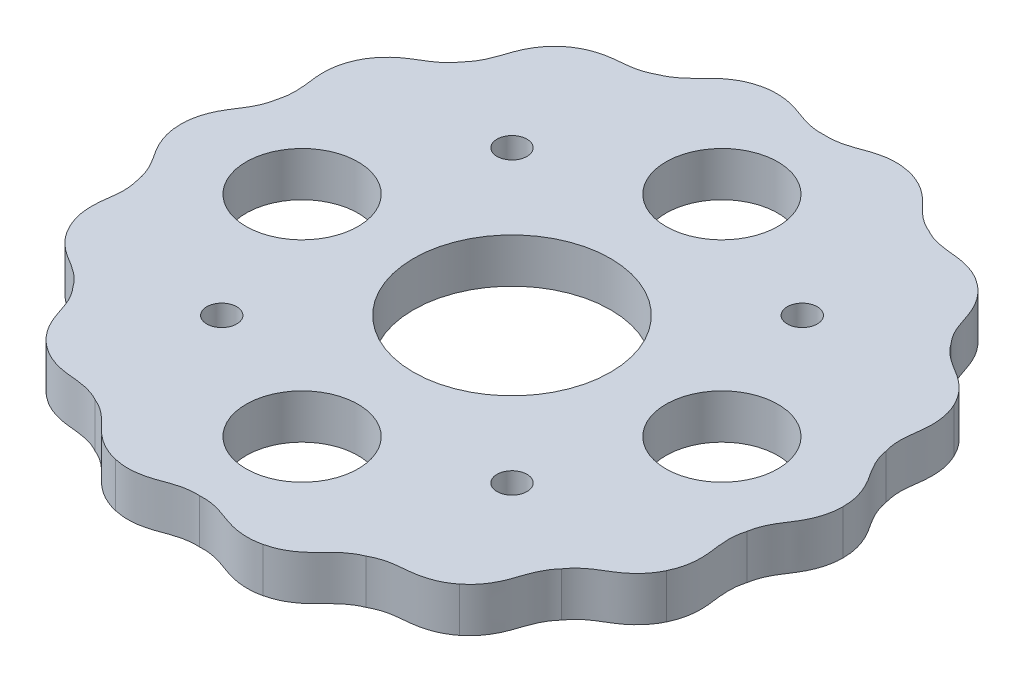
SolidWorks part; units mm, degrees
ref_plane "Front Plane" through (0, 0, 0) normal (0, 0, 1) x (1, 0, 0)
ref_plane "Top Plane" through (0, 0, 0) normal (0, 1, 0) x (1, 0, 0)
ref_plane "Right Plane" through (0, 0, 0) normal (1, 0, 0) x (0, 0, -1)
sketch "Sketch1" plane through (0, 0, 0) normal (0, 1, 0) x (1, 0, 0)
  line L0 (0, 0) -> (37.5, 0) construction
  line L1 (0, 0) -> (37.4807, 1.2019) construction
  line L2 (0, 0) -> (37.423, 2.4026) construction
  line L3 (0, 0) -> (37.3267, 3.6009) construction
  line L4 (0, 0) -> (37.1921, 4.7954) construction
  line L5 (0, 0) -> (37.0193, 5.985) construction
  line L6 (0, 0) -> (36.8085, 7.1684) construction
  line L7 (0, 0) -> (36.5598, 8.3445) construction
  line L8 (0, 0) -> (36.2736, 9.512) construction
  line L9 (0, 0) -> (35.95, 10.6698) construction
  line L10 (0, 0) -> (35.5896, 11.8166) construction
  line L11 (0, 0) -> (35.1926, 12.9512) construction
  line L12 (0, 0) -> (34.7594, 14.0725) construction
  line L13 (0, 0) -> (34.2905, 15.1794) construction
  line L14 (0, 0) -> (33.7863, 16.2706) construction
  line L15 (37.5, 0) -> (38.5, 0) construction
  line L16 (37.4807, 1.2019) -> (38.3521, 1.6927) construction
  line L17 (37.423, 2.4026) -> (37.9413, 3.2578) construction
  line L18 (37.3267, 3.6009) -> (37.3588, 4.6003) construction
  line L19 (37.1921, 4.7954) -> (36.7296, 5.682) construction
  line L20 (37.0193, 5.985) -> (36.1812, 6.5305) construction
  line L21 (36.8085, 7.1684) -> (35.8105, 7.2325) construction
  line L22 (36.5598, 8.3445) -> (35.5849, 8.122) construction
  line L23 (37, 0.0019) -> (37, 0)
  line L24 (33.3367, 16.052) -> (33.3358, 16.0537)
  line L25 (37, -0.0019) -> (37, 0)
  line L26 (33.3367, -16.052) -> (33.3358, -16.0537)
  line L27 (33.335, -16.0554) -> (33.3358, -16.0537)
  line L28 (23.0706, -28.9266) -> (23.0691, -28.9278)
  line L29 (23.0677, -28.9289) -> (23.0691, -28.9278)
  line L30 (8.2351, -36.0719) -> (8.2333, -36.0723)
  line L31 (8.2315, -36.0727) -> (8.2333, -36.0723)
  line L32 (-8.2315, -36.0727) -> (-8.2333, -36.0723)
  line L33 (-8.2351, -36.0719) -> (-8.2333, -36.0723)
  line L34 (-23.0677, -28.9289) -> (-23.0691, -28.9278)
  line L35 (-23.0706, -28.9266) -> (-23.0691, -28.9278)
  line L36 (-33.335, -16.0554) -> (-33.3358, -16.0537)
  line L37 (-33.3367, -16.052) -> (-33.3358, -16.0537)
  line L38 (-37, -0.0019) -> (-37, 0)
  line L39 (-37, 0.0019) -> (-37, 0)
  line L40 (-33.3367, 16.052) -> (-33.3358, 16.0537)
  line L41 (-33.335, 16.0554) -> (-33.3358, 16.0537)
  line L42 (-23.0706, 28.9266) -> (-23.0691, 28.9278)
  line L43 (-23.0677, 28.9289) -> (-23.0691, 28.9278)
  line L44 (-8.2351, 36.0719) -> (-8.2333, 36.0723)
  line L45 (-8.2315, 36.0727) -> (-8.2333, 36.0723)
  line L46 (8.2315, 36.0727) -> (8.2333, 36.0723)
  line L47 (8.2351, 36.0719) -> (8.2333, 36.0723)
  line L48 (23.0677, 28.9289) -> (23.0691, 28.9278)
  line L49 (23.0706, 28.9266) -> (23.0691, 28.9278)
  line L50 (33.335, 16.0554) -> (33.3358, 16.0537)
  line L51 (35.5, 0.0037) -> (35.5, 0)
  line L52 (31.986, 15.3995) -> (31.9844, 15.4029)
  line L53 (35.5, -0.0037) -> (35.5, 0)
  line L54 (31.986, -15.3995) -> (31.9844, -15.4029)
  line L55 (31.9828, -15.4062) -> (31.9844, -15.4029)
  line L56 (22.1368, -27.7527) -> (22.1339, -27.755)
  line L57 (22.131, -27.7573) -> (22.1339, -27.755)
  line L58 (7.9031, -34.6091) -> (7.8995, -34.6099)
  line L59 (7.8959, -34.6108) -> (7.8995, -34.6099)
  line L60 (-7.8959, -34.6108) -> (-7.8995, -34.6099)
  line L61 (-7.9031, -34.6091) -> (-7.8995, -34.6099)
  line L62 (-22.131, -27.7573) -> (-22.1339, -27.755)
  line L63 (-22.1368, -27.7527) -> (-22.1339, -27.755)
  line L64 (-31.9828, -15.4062) -> (-31.9844, -15.4029)
  line L65 (-31.986, -15.3995) -> (-31.9844, -15.4029)
  line L66 (-35.5, -0.0037) -> (-35.5, 0)
  line L67 (-35.5, 0.0037) -> (-35.5, 0)
  line L68 (-31.986, 15.3995) -> (-31.9844, 15.4029)
  line L69 (-31.9828, 15.4062) -> (-31.9844, 15.4029)
  line L70 (-22.1368, 27.7527) -> (-22.1339, 27.755)
  line L71 (-22.131, 27.7573) -> (-22.1339, 27.755)
  line L72 (-7.9031, 34.6091) -> (-7.8995, 34.6099)
  line L73 (-7.8959, 34.6108) -> (-7.8995, 34.6099)
  line L74 (7.8959, 34.6108) -> (7.8995, 34.6099)
  line L75 (7.9031, 34.6091) -> (7.8995, 34.6099)
  line L76 (22.131, 27.7573) -> (22.1339, 27.755)
  line L77 (22.1368, 27.7527) -> (22.1339, 27.755)
  line L78 (31.9828, 15.4062) -> (31.9844, 15.4029)
  circle A0 centre (0, 0) radius 35 construction
  circle A1 centre (37.5, 0) radius 2.5 construction
  circle A2 centre (0, 0) radius 37.5 construction
  spline S0 degree 3 poles (35.5849, 8.122) (35.6266, 7.5364) (36.0345, 6.7125) (36.7836, 5.6218) (37.4152, 4.5501) (38.2239, 2.702) (38.5014, 1.1074) (38.5, 0) knots 0 0 0 0 0.195516 0.310928 0.453873 0.621058 1 1 1 1
  spline S1 degree 3 poles (35.5849, 8.122) (35.3683, 8.6678) (35.3784, 9.5871) (35.5801, 10.8948) (35.6841, 12.1344) (35.611, 14.1503) (35.169, 15.7074) (34.6873, 16.7045) knots 0 0 0 0 0.195516 0.310928 0.453873 0.621058 1 1 1 1
  spline S2 degree 1 poles (34.1119, 7.7858) (33.3367, 16.052) knots 0 0 1 1 construction
  spline S3 degree 1 poles (34.1119, 7.7858) (37, 0.0019) knots 0 0 1 1 construction
  spline S4 degree 3 poles (33.3367, 16.052) (33.6005, 15.5058) (33.9037, 14.6401) (34.1146, 13.4372) (34.174, 12.5211) (34.1413, 11.5771) (34.0239, 10.6392) (33.8823, 9.6155) (33.9055, 8.625) (34.0243, 8.0514) (34.1119, 7.7858) knots 0.015853 0.015853 0.015853 0.015853 0.26189 0.384908 0.507927 0.630945 0.753963 0.876982 0.938491 1 1 1 1
  spline S5 degree 3 poles (34.1119, 7.7858) (34.1483, 7.5085) (34.2901, 6.9402) (34.6989, 6.0377) (35.2706, 5.1769) (35.7834, 4.3828) (36.2224, 3.5464) (36.5664, 2.6953) (36.8983, 1.52) (37.0008, 0.6085) (37, 0.0019) knots 0.015853 0.015853 0.015853 0.015853 0.077362 0.138872 0.26189 0.384908 0.507927 0.630945 0.753963 1 1 1 1
  spline S6 degree 3 poles (37, -0.0019) (37.0008, -0.6085) (36.8983, -1.52) (36.5664, -2.6953) (36.2224, -3.5464) (35.7834, -4.3828) (35.2706, -5.1769) (34.6989, -6.0377) (34.2901, -6.9402) (34.1483, -7.5085) (34.1119, -7.7858) knots 0.015853 0.015853 0.015853 0.015853 0.26189 0.384908 0.507927 0.630945 0.753963 0.876982 0.938491 1 1 1 1
  spline S7 degree 3 poles (34.1119, -7.7858) (34.0243, -8.0514) (33.9055, -8.625) (33.8823, -9.6155) (34.0239, -10.6392) (34.1413, -11.5771) (34.174, -12.5211) (34.1146, -13.4372) (33.9037, -14.6401) (33.6005, -15.5058) (33.3367, -16.052) knots 0.015853 0.015853 0.015853 0.015853 0.077362 0.138872 0.26189 0.384908 0.507927 0.630945 0.753963 1 1 1 1
  spline S8 degree 3 poles (33.335, -16.0554) (33.0725, -16.6022) (32.5847, -17.3791) (31.7758, -18.2939) (31.0965, -18.9115) (30.3381, -19.4746) (29.5316, -19.9675) (28.6429, -20.4951) (27.8831, -21.1308) (27.5087, -21.5813) (27.3556, -21.8154) knots 0.015853 0.015853 0.015853 0.015853 0.26189 0.384908 0.507927 0.630945 0.753963 0.876982 0.938491 1 1 1 1
  spline S9 degree 3 poles (27.3556, -21.8154) (27.1615, -22.0167) (26.8056, -22.4819) (26.3549, -23.3642) (26.0383, -24.348) (25.7371, -25.2439) (25.357, -26.1087) (24.906, -26.9083) (24.1941, -27.9005) (23.5453, -28.549) (23.0706, -28.9266) knots 0.015853 0.015853 0.015853 0.015853 0.077362 0.138872 0.26189 0.384908 0.507927 0.630945 0.753963 1 1 1 1
  spline S10 degree 3 poles (23.0677, -28.9289) (22.5939, -29.3077) (21.8173, -29.796) (20.6915, -30.2693) (19.8116, -30.531) (18.884, -30.7092) (17.9435, -30.8034) (16.9139, -30.8931) (15.9535, -31.1362) (15.4207, -31.3797) (15.1812, -31.5241) knots 0.015853 0.015853 0.015853 0.015853 0.26189 0.384908 0.507927 0.630945 0.753963 0.876982 0.938491 1 1 1 1
  spline S11 degree 3 poles (15.1812, -31.5241) (14.919, -31.6213) (14.3964, -31.886) (13.6076, -32.4854) (12.8955, -33.2344) (12.2354, -33.9109) (11.5177, -34.5251) (10.7645, -35.0499) (9.6926, -35.6349) (8.8266, -35.9377) (8.2351, -36.0719) knots 0.015853 0.015853 0.015853 0.015853 0.077362 0.138872 0.26189 0.384908 0.507927 0.630945 0.753963 1 1 1 1
  spline S12 degree 3 poles (8.2315, -36.0727) (7.6402, -36.2085) (6.7287, -36.3114) (5.5091, -36.2494) (4.6028, -36.1034) (3.6897, -35.8614) (2.8014, -35.5383) (1.8349, -35.1724) (0.8641, -34.9747) (0.2785, -34.9629) (0, -34.9891) knots 0.015853 0.015853 0.015853 0.015853 0.26189 0.384908 0.507927 0.630945 0.753963 0.876982 0.938491 1 1 1 1
  spline S13 degree 3 poles (0, -34.9891) (-0.2785, -34.9629) (-0.8641, -34.9747) (-1.8349, -35.1724) (-2.8014, -35.5383) (-3.6897, -35.8614) (-4.6028, -36.1034) (-5.5091, -36.2494) (-6.7287, -36.3114) (-7.6402, -36.2085) (-8.2315, -36.0727) knots 0.015853 0.015853 0.015853 0.015853 0.077362 0.138872 0.26189 0.384908 0.507927 0.630945 0.753963 1 1 1 1
  spline S14 degree 3 poles (-8.2351, -36.0719) (-8.8266, -35.9377) (-9.6926, -35.6349) (-10.7645, -35.0499) (-11.5177, -34.5251) (-12.2354, -33.9109) (-12.8955, -33.2344) (-13.6076, -32.4854) (-14.3964, -31.886) (-14.919, -31.6213) (-15.1812, -31.5241) knots 0.015853 0.015853 0.015853 0.015853 0.26189 0.384908 0.507927 0.630945 0.753963 0.876982 0.938491 1 1 1 1
  spline S15 degree 3 poles (-15.1812, -31.5241) (-15.4207, -31.3797) (-15.9535, -31.1362) (-16.9139, -30.8931) (-17.9435, -30.8034) (-18.884, -30.7092) (-19.8116, -30.531) (-20.6915, -30.2693) (-21.8173, -29.796) (-22.5939, -29.3077) (-23.0677, -28.9289) knots 0.015853 0.015853 0.015853 0.015853 0.077362 0.138872 0.26189 0.384908 0.507927 0.630945 0.753963 1 1 1 1
  spline S16 degree 3 poles (-23.0706, -28.9266) (-23.5453, -28.549) (-24.1941, -27.9005) (-24.906, -26.9083) (-25.357, -26.1087) (-25.7371, -25.2439) (-26.0383, -24.348) (-26.3549, -23.3642) (-26.8056, -22.4819) (-27.1615, -22.0167) (-27.3556, -21.8154) knots 0.015853 0.015853 0.015853 0.015853 0.26189 0.384908 0.507927 0.630945 0.753963 0.876982 0.938491 1 1 1 1
  spline S17 degree 3 poles (-27.3556, -21.8154) (-27.5087, -21.5813) (-27.8831, -21.1308) (-28.6429, -20.4951) (-29.5316, -19.9675) (-30.3381, -19.4746) (-31.0965, -18.9115) (-31.7758, -18.2939) (-32.5847, -17.3791) (-33.0725, -16.6022) (-33.335, -16.0554) knots 0.015853 0.015853 0.015853 0.015853 0.077362 0.138872 0.26189 0.384908 0.507927 0.630945 0.753963 1 1 1 1
  spline S18 degree 3 poles (-33.3367, -16.052) (-33.6005, -15.5058) (-33.9037, -14.6401) (-34.1146, -13.4372) (-34.174, -12.5211) (-34.1413, -11.5771) (-34.0239, -10.6392) (-33.8823, -9.6155) (-33.9055, -8.625) (-34.0243, -8.0514) (-34.1119, -7.7858) knots 0.015853 0.015853 0.015853 0.015853 0.26189 0.384908 0.507927 0.630945 0.753963 0.876982 0.938491 1 1 1 1
  spline S19 degree 3 poles (-34.1119, -7.7858) (-34.1483, -7.5085) (-34.2901, -6.9402) (-34.6989, -6.0377) (-35.2706, -5.1769) (-35.7834, -4.3828) (-36.2224, -3.5464) (-36.5664, -2.6953) (-36.8983, -1.52) (-37.0008, -0.6085) (-37, -0.0019) knots 0.015853 0.015853 0.015853 0.015853 0.077362 0.138872 0.26189 0.384908 0.507927 0.630945 0.753963 1 1 1 1
  spline S20 degree 3 poles (-37, 0.0019) (-37.0008, 0.6085) (-36.8983, 1.52) (-36.5664, 2.6953) (-36.2224, 3.5464) (-35.7834, 4.3828) (-35.2706, 5.1769) (-34.6989, 6.0377) (-34.2901, 6.9402) (-34.1483, 7.5085) (-34.1119, 7.7858) knots 0.015853 0.015853 0.015853 0.015853 0.26189 0.384908 0.507927 0.630945 0.753963 0.876982 0.938491 1 1 1 1
  spline S21 degree 3 poles (-34.1119, 7.7858) (-34.0243, 8.0514) (-33.9055, 8.625) (-33.8823, 9.6155) (-34.0239, 10.6392) (-34.1413, 11.5771) (-34.174, 12.5211) (-34.1146, 13.4372) (-33.9037, 14.6401) (-33.6005, 15.5058) (-33.3367, 16.052) knots 0.015853 0.015853 0.015853 0.015853 0.077362 0.138872 0.26189 0.384908 0.507927 0.630945 0.753963 1 1 1 1
  spline S22 degree 3 poles (-33.335, 16.0554) (-33.0725, 16.6022) (-32.5847, 17.3791) (-31.7758, 18.2939) (-31.0965, 18.9115) (-30.3381, 19.4746) (-29.5316, 19.9675) (-28.6429, 20.4951) (-27.8831, 21.1308) (-27.5087, 21.5813) (-27.3556, 21.8154) knots 0.015853 0.015853 0.015853 0.015853 0.26189 0.384908 0.507927 0.630945 0.753963 0.876982 0.938491 1 1 1 1
  spline S23 degree 3 poles (-27.3556, 21.8154) (-27.1615, 22.0167) (-26.8056, 22.4819) (-26.3549, 23.3642) (-26.0383, 24.348) (-25.7371, 25.2439) (-25.357, 26.1087) (-24.906, 26.9083) (-24.1941, 27.9005) (-23.5453, 28.549) (-23.0706, 28.9266) knots 0.015853 0.015853 0.015853 0.015853 0.077362 0.138872 0.26189 0.384908 0.507927 0.630945 0.753963 1 1 1 1
  spline S24 degree 3 poles (-23.0677, 28.9289) (-22.5939, 29.3077) (-21.8173, 29.796) (-20.6915, 30.2693) (-19.8116, 30.531) (-18.884, 30.7092) (-17.9435, 30.8034) (-16.9139, 30.8931) (-15.9535, 31.1362) (-15.4207, 31.3797) (-15.1812, 31.5241) knots 0.015853 0.015853 0.015853 0.015853 0.26189 0.384908 0.507927 0.630945 0.753963 0.876982 0.938491 1 1 1 1
  spline S25 degree 3 poles (-15.1812, 31.5241) (-14.919, 31.6213) (-14.3964, 31.886) (-13.6076, 32.4854) (-12.8955, 33.2344) (-12.2354, 33.9109) (-11.5177, 34.5251) (-10.7645, 35.0499) (-9.6926, 35.6349) (-8.8266, 35.9377) (-8.2351, 36.0719) knots 0.015853 0.015853 0.015853 0.015853 0.077362 0.138872 0.26189 0.384908 0.507927 0.630945 0.753963 1 1 1 1
  spline S26 degree 3 poles (-8.2315, 36.0727) (-7.6402, 36.2085) (-6.7287, 36.3114) (-5.5091, 36.2494) (-4.6028, 36.1034) (-3.6897, 35.8614) (-2.8014, 35.5383) (-1.8349, 35.1724) (-0.8641, 34.9747) (-0.2785, 34.9629) (0, 34.9891) knots 0.015853 0.015853 0.015853 0.015853 0.26189 0.384908 0.507927 0.630945 0.753963 0.876982 0.938491 1 1 1 1
  spline S27 degree 3 poles (0, 34.9891) (0.2785, 34.9629) (0.8641, 34.9747) (1.8349, 35.1724) (2.8014, 35.5383) (3.6897, 35.8614) (4.6028, 36.1034) (5.5091, 36.2494) (6.7287, 36.3114) (7.6402, 36.2085) (8.2315, 36.0727) knots 0.015853 0.015853 0.015853 0.015853 0.077362 0.138872 0.26189 0.384908 0.507927 0.630945 0.753963 1 1 1 1
  spline S28 degree 3 poles (8.2351, 36.0719) (8.8266, 35.9377) (9.6926, 35.6349) (10.7645, 35.0499) (11.5177, 34.5251) (12.2354, 33.9109) (12.8955, 33.2344) (13.6076, 32.4854) (14.3964, 31.886) (14.919, 31.6213) (15.1812, 31.5241) knots 0.015853 0.015853 0.015853 0.015853 0.26189 0.384908 0.507927 0.630945 0.753963 0.876982 0.938491 1 1 1 1
  spline S29 degree 3 poles (15.1812, 31.5241) (15.4207, 31.3797) (15.9535, 31.1362) (16.9139, 30.8931) (17.9435, 30.8034) (18.884, 30.7092) (19.8116, 30.531) (20.6915, 30.2693) (21.8173, 29.796) (22.5939, 29.3077) (23.0677, 28.9289) knots 0.015853 0.015853 0.015853 0.015853 0.077362 0.138872 0.26189 0.384908 0.507927 0.630945 0.753963 1 1 1 1
  spline S30 degree 3 poles (23.0706, 28.9266) (23.5453, 28.549) (24.1941, 27.9005) (24.906, 26.9083) (25.357, 26.1087) (25.7371, 25.2439) (26.0383, 24.348) (26.3549, 23.3642) (26.8056, 22.4819) (27.1615, 22.0167) (27.3556, 21.8154) knots 0.015853 0.015853 0.015853 0.015853 0.26189 0.384908 0.507927 0.630945 0.753963 0.876982 0.938491 1 1 1 1
  spline S31 degree 3 poles (27.3556, 21.8154) (27.5087, 21.5813) (27.8831, 21.1308) (28.6429, 20.4951) (29.5316, 19.9675) (30.3381, 19.4746) (31.0965, 18.9115) (31.7758, 18.2939) (32.5847, 17.3791) (33.0725, 16.6022) (33.335, 16.0554) knots 0.015853 0.015853 0.015853 0.015853 0.077362 0.138872 0.26189 0.384908 0.507927 0.630945 0.753963 1 1 1 1
  spline S32 degree 1 poles (32.6448, 7.451) (35.5, 0.0037) knots 0 0 1 1 construction
  spline S33 degree 1 poles (32.6448, 7.451) (31.986, 15.3995) knots 0 0 1 1 construction
  spline S34 degree 3 poles (35.5, 0.0037) (35.5006, 0.4959) (35.4183, 1.2336) (35.1496, 2.1927) (34.8707, 2.8896) (34.4997, 3.6015) (34.1394, 4.1652) (33.6939, 4.8394) (33.3068, 5.4873) (32.9751, 6.1975) (32.758, 6.8733) (32.6748, 7.2607) (32.6448, 7.451) knots 0.023011 0.023011 0.023011 0.023011 0.267258 0.389382 0.511505 0.633629 0.755753 0.816814 0.877876 0.938938 0.969469 1 1 1 1
  spline S35 degree 3 poles (32.6448, 7.451) (32.5893, 7.6354) (32.4961, 8.0206) (32.3985, 8.7236) (32.3893, 9.5074) (32.4569, 10.2591) (32.5657, 11.0598) (32.6458, 11.724) (32.6712, 12.5264) (32.6201, 13.2752) (32.446, 14.256) (32.2001, 14.9563) (31.986, 15.3995) knots 0.023011 0.023011 0.023011 0.023011 0.053542 0.084072 0.145134 0.206196 0.267258 0.389382 0.511505 0.633629 0.755753 1 1 1 1
  spline S36 degree 3 poles (32.6448, -7.451) (32.6748, -7.2607) (32.758, -6.8733) (32.9751, -6.1975) (33.3068, -5.4873) (33.6939, -4.8394) (34.1394, -4.1652) (34.4997, -3.6015) (34.8707, -2.8896) (35.1496, -2.1927) (35.4183, -1.2336) (35.5006, -0.4959) (35.5, -0.0037) knots 0.023011 0.023011 0.023011 0.023011 0.053542 0.084072 0.145134 0.206196 0.267258 0.389382 0.511505 0.633629 0.755753 1 1 1 1
  spline S37 degree 3 poles (31.986, -15.3995) (32.2001, -14.9563) (32.446, -14.256) (32.6201, -13.2752) (32.6712, -12.5264) (32.6458, -11.724) (32.5657, -11.0598) (32.4569, -10.2591) (32.3893, -9.5074) (32.3985, -8.7236) (32.4961, -8.0206) (32.5893, -7.6354) (32.6448, -7.451) knots 0.023011 0.023011 0.023011 0.023011 0.267258 0.389382 0.511505 0.633629 0.755753 0.816814 0.877876 0.938938 0.969469 1 1 1 1
  spline S38 degree 3 poles (26.1791, -20.8771) (26.2887, -20.7187) (26.5317, -20.4057) (27.0205, -19.8911) (27.6275, -19.3952) (28.2574, -18.9793) (28.9513, -18.5652) (29.5206, -18.2137) (30.1637, -17.7333) (30.7173, -17.2264) (31.3755, -16.4789) (31.7698, -15.8499) (31.9828, -15.4062) knots 0.023011 0.023011 0.023011 0.023011 0.053542 0.084072 0.145134 0.206196 0.267258 0.389382 0.511505 0.633629 0.755753 1 1 1 1
  spline S39 degree 3 poles (22.1368, -27.7527) (22.522, -27.4463) (23.0474, -26.922) (23.6297, -26.1139) (24.0007, -25.4614) (24.326, -24.7275) (24.542, -24.0943) (24.7914, -23.3257) (25.0566, -22.619) (25.405, -21.9169) (25.798, -21.3258) (26.0491, -21.0192) (26.1791, -20.8771) knots 0.023011 0.023011 0.023011 0.023011 0.267258 0.389382 0.511505 0.633629 0.755753 0.816814 0.877876 0.938938 0.969469 1 1 1 1
  spline S40 degree 3 poles (14.5283, -30.1683) (14.6957, -30.0732) (15.0505, -29.8966) (15.7143, -29.645) (16.4763, -29.4616) (17.2242, -29.3602) (18.0291, -29.2882) (18.6945, -29.2185) (19.4823, -29.0647) (20.201, -28.8482) (21.1184, -28.4603) (21.7465, -28.0647) (22.131, -27.7573) knots 0.023011 0.023011 0.023011 0.023011 0.053542 0.084072 0.145134 0.206196 0.267258 0.389382 0.511505 0.633629 0.755753 1 1 1 1
  spline S41 degree 3 poles (7.9031, -34.6091) (8.3831, -34.5002) (9.084, -34.2557) (9.9593, -33.7804) (10.5766, -33.3534) (11.1881, -32.8334) (11.6575, -32.3566) (12.2156, -31.7723) (12.7612, -31.2507) (13.3797, -30.7693) (13.9903, -30.4072) (14.3495, -30.2399) (14.5283, -30.1683) knots 0.023011 0.023011 0.023011 0.023011 0.267258 0.389382 0.511505 0.633629 0.755753 0.816814 0.877876 0.938938 0.969469 1 1 1 1
  spline S42 degree 3 poles (0, -33.4843) (0.1922, -33.4712) (0.5884, -33.4661) (1.2956, -33.5274) (2.0617, -33.6928) (2.7796, -33.926) (3.536, -34.2103) (4.1657, -34.4362) (4.9423, -34.6394) (5.6838, -34.7562) (6.6786, -34.8048) (7.4161, -34.7209) (7.8959, -34.6108) knots 0.023011 0.023011 0.023011 0.023011 0.053542 0.084072 0.145134 0.206196 0.267258 0.389382 0.511505 0.633629 0.755753 1 1 1 1
  spline S43 degree 3 poles (-7.8959, -34.6108) (-7.4161, -34.7209) (-6.6786, -34.8048) (-5.6838, -34.7562) (-4.9423, -34.6394) (-4.1657, -34.4362) (-3.536, -34.2103) (-2.7796, -33.926) (-2.0617, -33.6928) (-1.2956, -33.5274) (-0.5884, -33.4661) (-0.1922, -33.4712) (0, -33.4843) knots 0.023011 0.023011 0.023011 0.023011 0.267258 0.389382 0.511505 0.633629 0.755753 0.816814 0.877876 0.938938 0.969469 1 1 1 1
  spline S44 degree 3 poles (-14.5283, -30.1683) (-14.3495, -30.2399) (-13.9903, -30.4072) (-13.3797, -30.7693) (-12.7612, -31.2507) (-12.2156, -31.7723) (-11.6575, -32.3566) (-11.1881, -32.8334) (-10.5766, -33.3534) (-9.9593, -33.7804) (-9.084, -34.2557) (-8.3831, -34.5002) (-7.9031, -34.6091) knots 0.023011 0.023011 0.023011 0.023011 0.053542 0.084072 0.145134 0.206196 0.267258 0.389382 0.511505 0.633629 0.755753 1 1 1 1
  spline S45 degree 3 poles (-22.131, -27.7573) (-21.7465, -28.0647) (-21.1184, -28.4603) (-20.201, -28.8482) (-19.4823, -29.0647) (-18.6945, -29.2185) (-18.0291, -29.2882) (-17.2242, -29.3602) (-16.4763, -29.4616) (-15.7143, -29.645) (-15.0505, -29.8966) (-14.6957, -30.0732) (-14.5283, -30.1683) knots 0.023011 0.023011 0.023011 0.023011 0.267258 0.389382 0.511505 0.633629 0.755753 0.816814 0.877876 0.938938 0.969469 1 1 1 1
  spline S46 degree 3 poles (-26.1791, -20.8771) (-26.0491, -21.0192) (-25.798, -21.3258) (-25.405, -21.9169) (-25.0566, -22.619) (-24.7914, -23.3257) (-24.542, -24.0943) (-24.326, -24.7275) (-24.0007, -25.4614) (-23.6297, -26.1139) (-23.0474, -26.922) (-22.522, -27.4463) (-22.1368, -27.7527) knots 0.023011 0.023011 0.023011 0.023011 0.053542 0.084072 0.145134 0.206196 0.267258 0.389382 0.511505 0.633629 0.755753 1 1 1 1
  spline S47 degree 3 poles (-31.9828, -15.4062) (-31.7698, -15.8499) (-31.3755, -16.4789) (-30.7173, -17.2264) (-30.1637, -17.7333) (-29.5206, -18.2137) (-28.9513, -18.5652) (-28.2574, -18.9793) (-27.6275, -19.3952) (-27.0205, -19.8911) (-26.5317, -20.4057) (-26.2887, -20.7187) (-26.1791, -20.8771) knots 0.023011 0.023011 0.023011 0.023011 0.267258 0.389382 0.511505 0.633629 0.755753 0.816814 0.877876 0.938938 0.969469 1 1 1 1
  spline S48 degree 3 poles (-32.6448, -7.451) (-32.5893, -7.6354) (-32.4961, -8.0206) (-32.3985, -8.7236) (-32.3893, -9.5074) (-32.4569, -10.2591) (-32.5657, -11.0598) (-32.6458, -11.724) (-32.6712, -12.5264) (-32.6201, -13.2752) (-32.446, -14.256) (-32.2001, -14.9563) (-31.986, -15.3995) knots 0.023011 0.023011 0.023011 0.023011 0.053542 0.084072 0.145134 0.206196 0.267258 0.389382 0.511505 0.633629 0.755753 1 1 1 1
  spline S49 degree 3 poles (-35.5, -0.0037) (-35.5006, -0.4959) (-35.4183, -1.2336) (-35.1496, -2.1927) (-34.8707, -2.8896) (-34.4997, -3.6015) (-34.1394, -4.1652) (-33.6939, -4.8394) (-33.3068, -5.4873) (-32.9751, -6.1975) (-32.758, -6.8733) (-32.6748, -7.2607) (-32.6448, -7.451) knots 0.023011 0.023011 0.023011 0.023011 0.267258 0.389382 0.511505 0.633629 0.755753 0.816814 0.877876 0.938938 0.969469 1 1 1 1
  spline S50 degree 3 poles (-32.6448, 7.451) (-32.6748, 7.2607) (-32.758, 6.8733) (-32.9751, 6.1975) (-33.3068, 5.4873) (-33.6939, 4.8394) (-34.1394, 4.1652) (-34.4997, 3.6015) (-34.8707, 2.8896) (-35.1496, 2.1927) (-35.4183, 1.2336) (-35.5006, 0.4959) (-35.5, 0.0037) knots 0.023011 0.023011 0.023011 0.023011 0.053542 0.084072 0.145134 0.206196 0.267258 0.389382 0.511505 0.633629 0.755753 1 1 1 1
  spline S51 degree 3 poles (-31.986, 15.3995) (-32.2001, 14.9563) (-32.446, 14.256) (-32.6201, 13.2752) (-32.6712, 12.5264) (-32.6458, 11.724) (-32.5657, 11.0598) (-32.4569, 10.2591) (-32.3893, 9.5074) (-32.3985, 8.7236) (-32.4961, 8.0206) (-32.5893, 7.6354) (-32.6448, 7.451) knots 0.023011 0.023011 0.023011 0.023011 0.267258 0.389382 0.511505 0.633629 0.755753 0.816814 0.877876 0.938938 0.969469 1 1 1 1
  spline S52 degree 3 poles (-26.1791, 20.8771) (-26.2887, 20.7187) (-26.5317, 20.4057) (-27.0205, 19.8911) (-27.6275, 19.3952) (-28.2574, 18.9793) (-28.9513, 18.5652) (-29.5206, 18.2137) (-30.1637, 17.7333) (-30.7173, 17.2264) (-31.3755, 16.4789) (-31.7698, 15.8499) (-31.9828, 15.4062) knots 0.023011 0.023011 0.023011 0.023011 0.053542 0.084072 0.145134 0.206196 0.267258 0.389382 0.511505 0.633629 0.755753 1 1 1 1
  spline S53 degree 3 poles (-22.1368, 27.7527) (-22.522, 27.4463) (-23.0474, 26.922) (-23.6297, 26.1139) (-24.0007, 25.4614) (-24.326, 24.7275) (-24.542, 24.0943) (-24.7914, 23.3257) (-25.0566, 22.619) (-25.405, 21.9169) (-25.798, 21.3258) (-26.0491, 21.0192) (-26.1791, 20.8771) knots 0.023011 0.023011 0.023011 0.023011 0.267258 0.389382 0.511505 0.633629 0.755753 0.816814 0.877876 0.938938 0.969469 1 1 1 1
  spline S54 degree 3 poles (-14.5283, 30.1683) (-14.6957, 30.0732) (-15.0505, 29.8966) (-15.7143, 29.645) (-16.4763, 29.4616) (-17.2242, 29.3602) (-18.0291, 29.2882) (-18.6945, 29.2185) (-19.4823, 29.0647) (-20.201, 28.8482) (-21.1184, 28.4603) (-21.7465, 28.0647) (-22.131, 27.7573) knots 0.023011 0.023011 0.023011 0.023011 0.053542 0.084072 0.145134 0.206196 0.267258 0.389382 0.511505 0.633629 0.755753 1 1 1 1
  spline S55 degree 3 poles (-7.9031, 34.6091) (-8.3831, 34.5002) (-9.084, 34.2557) (-9.9593, 33.7804) (-10.5766, 33.3534) (-11.1881, 32.8334) (-11.6575, 32.3566) (-12.2156, 31.7723) (-12.7612, 31.2507) (-13.3797, 30.7693) (-13.9903, 30.4072) (-14.3495, 30.2399) (-14.5283, 30.1683) knots 0.023011 0.023011 0.023011 0.023011 0.267258 0.389382 0.511505 0.633629 0.755753 0.816814 0.877876 0.938938 0.969469 1 1 1 1
  spline S56 degree 3 poles (0, 33.4843) (-0.1922, 33.4712) (-0.5884, 33.4661) (-1.2956, 33.5274) (-2.0617, 33.6928) (-2.7796, 33.926) (-3.536, 34.2103) (-4.1657, 34.4362) (-4.9423, 34.6394) (-5.6838, 34.7562) (-6.6786, 34.8048) (-7.4161, 34.7209) (-7.8959, 34.6108) knots 0.023011 0.023011 0.023011 0.023011 0.053542 0.084072 0.145134 0.206196 0.267258 0.389382 0.511505 0.633629 0.755753 1 1 1 1
  spline S57 degree 3 poles (7.8959, 34.6108) (7.4161, 34.7209) (6.6786, 34.8048) (5.6838, 34.7562) (4.9423, 34.6394) (4.1657, 34.4362) (3.536, 34.2103) (2.7796, 33.926) (2.0617, 33.6928) (1.2956, 33.5274) (0.5884, 33.4661) (0.1922, 33.4712) (0, 33.4843) knots 0.023011 0.023011 0.023011 0.023011 0.267258 0.389382 0.511505 0.633629 0.755753 0.816814 0.877876 0.938938 0.969469 1 1 1 1
  spline S58 degree 3 poles (14.5283, 30.1683) (14.3495, 30.2399) (13.9903, 30.4072) (13.3797, 30.7693) (12.7612, 31.2507) (12.2156, 31.7723) (11.6575, 32.3566) (11.1881, 32.8334) (10.5766, 33.3534) (9.9593, 33.7804) (9.084, 34.2557) (8.3831, 34.5002) (7.9031, 34.6091) knots 0.023011 0.023011 0.023011 0.023011 0.053542 0.084072 0.145134 0.206196 0.267258 0.389382 0.511505 0.633629 0.755753 1 1 1 1
  spline S59 degree 3 poles (22.131, 27.7573) (21.7465, 28.0647) (21.1184, 28.4603) (20.201, 28.8482) (19.4823, 29.0647) (18.6945, 29.2185) (18.0291, 29.2882) (17.2242, 29.3602) (16.4763, 29.4616) (15.7143, 29.645) (15.0505, 29.8966) (14.6957, 30.0732) (14.5283, 30.1683) knots 0.023011 0.023011 0.023011 0.023011 0.267258 0.389382 0.511505 0.633629 0.755753 0.816814 0.877876 0.938938 0.969469 1 1 1 1
  spline S60 degree 3 poles (26.1791, 20.8771) (26.0491, 21.0192) (25.798, 21.3258) (25.405, 21.9169) (25.0566, 22.619) (24.7914, 23.3257) (24.542, 24.0943) (24.326, 24.7275) (24.0007, 25.4614) (23.6297, 26.1139) (23.0474, 26.922) (22.522, 27.4463) (22.1368, 27.7527) knots 0.023011 0.023011 0.023011 0.023011 0.053542 0.084072 0.145134 0.206196 0.267258 0.389382 0.511505 0.633629 0.755753 1 1 1 1
  spline S61 degree 3 poles (31.9828, 15.4062) (31.7698, 15.8499) (31.3755, 16.4789) (30.7173, 17.2264) (30.1637, 17.7333) (29.5206, 18.2137) (28.9513, 18.5652) (28.2574, 18.9793) (27.6275, 19.3952) (27.0205, 19.8911) (26.5317, 20.4057) (26.2887, 20.7187) (26.1791, 20.8771) knots 0.023011 0.023011 0.023011 0.023011 0.267258 0.389382 0.511505 0.633629 0.755753 0.816814 0.877876 0.938938 0.969469 1 1 1 1
  point P25 (0, 0)
  point P117 (0, 0)
  point P174 (0, 0)
  dimension "D1" = 70
  dimension "D2" = 5
  dimension "D4" = 25.714
  dimension "D5" = 1
  dimension "D7" = 180
  dimension "D8" = 207.551
  dimension "D6" = 1
  dimension "D9" = 1
  dimension "D10" = 235.102
  dimension "D11" = 1
  dimension "D12" = 1
  dimension "D13" = 1
  dimension "D14" = 1
  dimension "D15" = 1
  dimension "D16" = 262.653
  dimension "D17" = 290.204
  dimension "D18" = 317.755
  dimension "D19" = 345.306
  dimension "D20" = 1.5
  dimension "D22" = 3
  dimension "D3" = 15
  dimension "D21" = 14
  dimension "D23" = 14
extrude "Boss-Extrude3" add sketch "Sketch1" along normal blind 4.7625 contours L51 L53 S36 S37 L54 L55 S38 S39 L56 L57 S40 S41 L58 L59 S42 S43 L60 L61 S44 S45 L62 L63 S46 S47 L64 L65 S48 S49 L66 L67 S50 S51 L68 L69 S52 S53 L70 L71 S54 S55 L72 L73 S56 S57 L74 L75 S58 S59 L76 L77 S60 S61 L78 L52 S35 S34
sketch "Sketch2" plane through (0, 4.7625, 0) normal (0, 1, 0) x (1, 0, 0)
  line L0 (0, 0) -> (22.5, 0) construction
  line L1 (0, 0) -> (15.5563, 15.5563) construction
  circle A0 centre (0, 0) radius 10.5635
  circle A1 centre (22.5, 0) radius 6
  circle A6 centre (15.5563, 15.5563) radius 1.607
  circle A7 centre (0, -22.5) radius 6
  circle A8 centre (15.5563, -15.5563) radius 1.607
  circle A9 centre (-22.5, 0) radius 6
  circle A10 centre (-15.5563, -15.5563) radius 1.607
  circle A11 centre (0, 22.5) radius 6
  circle A12 centre (-15.5563, 15.5563) radius 1.607
  point P16 (0, 0)
  point P21 (0, 0)
  point P24 (0, 0)
  dimension "D3" = 12
  dimension "D1" = 21.127
  dimension "D6" = 3.214
  dimension "D2" = 22.5
  dimension "D4" = 45
  dimension "D5" = 22
  dimension "D7" = 4
extrude "Cut-Extrude1" cut sketch "Sketch2" against normal blind 4.7625 contours A7 | A0 | A0 | A0 | L0 A0 | A0 L0 | A1 | A9 | A11 region at (0, 4.7625, 0) region at (22.5, 4.7625, 0) region at (0, 4.7625, 22.5) region at (-22.5, 4.7625, 0) region at (0, 4.7625, -22.5)
extrude "Cut-Extrude2" cut sketch "Sketch2<4>" against normal blind 2.4105 contours A12 | A10 | A8 | A6 region at (15.5563, 4.7625, -15.5563) region at (15.5563, 4.7625, 15.5563) region at (-15.5563, 4.7625, 15.5563) region at (-15.5563, 4.7625, -15.5563)
sketch "Sketch2<4>" plane through (0, 4.7625, 0) normal (0, 1, 0) x (1, 0, 0) same geometry as "Sketch2"
equation "\"D5@Sketch1\" = \"eccentricity\""
equation "\"D6@Sketch1\" = \"eccentricity\""
equation "\"D9@Sketch1\" = \"eccentricity\""
equation "\"D11@Sketch1\" = \"eccentricity\""
equation "\"D12@Sketch1\" = \"eccentricity\""
equation "\"D14@Sketch1\" = \"eccentricity\""
equation "\"D13@Sketch1\" = \"eccentricity\""
equation "\"D15@Sketch1\"= \"eccentricity\""
equation "\"D1@Sketch2\"=\"largeBearOD\"+\"largeBearOTight\""
equation "\"D1@Cut-Extrude2\"=\"ballBearDiam\" * 0.75"
equation "\"D1@Boss-Extrude3\"=\"sheetThickness\""
equation "\"smallBearOD\"= 15mm"
equation "\"smallBearID\" = 0mm"
equation "\"smallBearOTight\"= 0mm'calibrate - hold onto bottom of gearbox"
equation "\"smallBearOLoose\"= 0mm'calibrate - able to take off topHat"
equation "\"smallBearITight\" = 0mm'hold onto "
equation "\"pinCircleDiam\"= 75mm"
equation "\"pinDiam\"= 6mm"
equation "\"sheetThickness\"= 0.1875in"
equation "\"D6@Sketch2\"=\"ballBearDiam\""
equation "\"largeBearOD\"= 21mm"
equation "\"largeBearID\" = 15mm"
equation "\"largeBearOTight\"= 0.127mm'calibrate - hold onto gears"
equation "\"largeBearITight\"= 0mm'calibrate - hold onto eccentric nut"
equation "\"ballBearDiam\"= 3.214mm"
equation "\"thrustBearingThickness\"= 5mm'measure this irl and change"
equation "\"thrustBearingID\"= 0mm'measure this irl and change"
equation "\"thrustBearingOD\"= 0mm'measure this irl and change"
equation "\"eccentricity\" = 1mm"
equation "\"D1@Cut-Extrude1\"=\"sheetThickness\""
